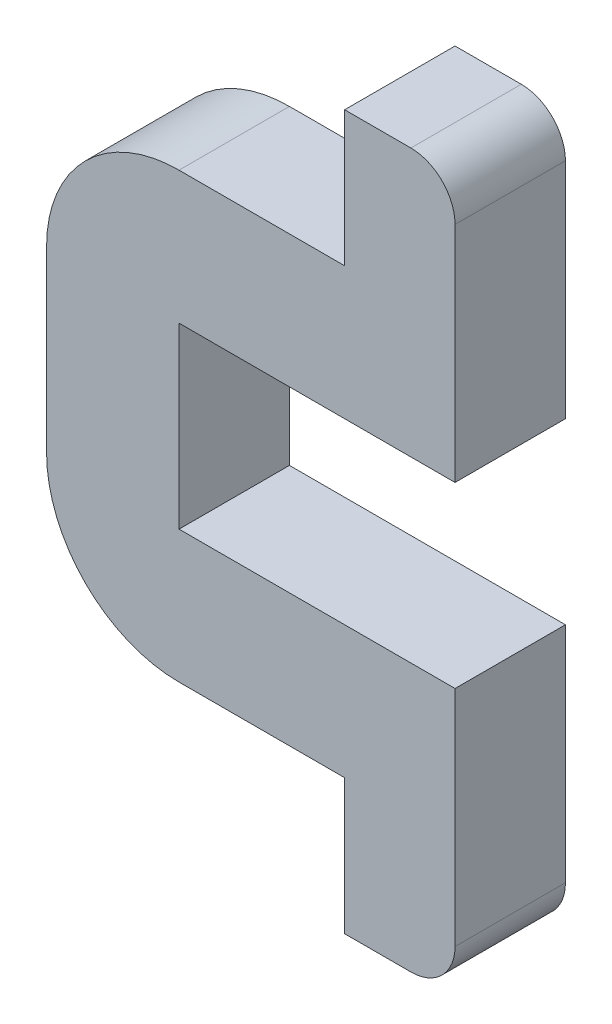
SolidWorks part; units mm, degrees
material "PBT General Purpose"
ref_plane "Front Plane" through (0, 0, 0) normal (0, 0, 1) x (1, 0, 0)
ref_plane "Top Plane" through (0, 0, 0) normal (0, 1, 0) x (1, 0, 0)
ref_plane "Right Plane" through (0, 0, 0) normal (1, 0, 0) x (0, 0, -1)
sketch "frame_outline" plane through (0, 0, 0) normal (0, 0, 1) x (1, 0, 0)
  line L0 (0, 0) -> (-0.625, 0)
  line L1 (-0.625, 0) -> (-0.625, 0.404)
  line L2 (-0.625, 0.404) -> (0, 0.404)
  line L3 (0, 0.404) -> (0, 1.01)
  line L71 (0, 1.01) -> (-0.25, 1.01)
  line L90 (-0.25, 1.01) -> (-0.25, 0.704)
  line L91 (-0.25, 0.704) -> (-0.925, 0.704)
  line L93 (-0.925, 0.704) -> (-0.925, -0.3)
  line L95 (-0.925, -0.3) -> (-0.25, -0.3)
  line L96 (-0.25, -0.3) -> (-0.25, -0.606)
  line L97 (-0.25, -0.606) -> (0, -0.606)
  line L98 (0, -0.606) -> (0, 0)
  dimension "D3" = 0.404
  dimension "D4" = 0.625
  dimension "D5" = 0.25
  dimension "D6" = 0.3
  dimension "D7" = 0.306
  dimension "D8" = 0.3
extrude "Boss-Extrude1" add sketch "frame_outline" along normal mid plane 0.25
fillet "Fillet1" radius 0.3 2 edges at (-0.925, -0.3, 0) (-0.925, 0.704, 0)
fillet "Fillet2" radius 0.1 2 edges at (0, 1.01, 0) (0, -0.606, 0)
equation "\"t\"= 0.25'thickness of the sheets"
equation "\"t_cf\" = 0.115'thickness of single carbon fiber layer"
equation "\"t_kapton\" = 0.025'thickness of single Kapton flex layer"
equation "\"t_fr4\" = 0.1'thickness of FR4 with copper layer"
equation "\"joint_flex\"= 0.1'Width of flextures gap"
equation "\"joint_flex_eff\"= 0.02'Width of flecture after castelation"
equation "\"joint_fold\"= 0.2'Width of folding joints for 90deg fold"
equation "\"gap_tolerance\"= 0.002'Width to have interfecence fit between carbon fiber inserts"
equation "\"assemble_angle\"= 90'Angle of assembly parts"
equation "\"D1@Boss-Extrude1\"=\"t\""
equation "\"D3@frame_outline\"=0.4+\"gap_tolerance\"*2"
equation "\"D4@frame_outline\"=\"t\"*2.5"
equation "\"D5@frame_outline\"=\"t\""
equation "\"D7@frame_outline\"=0.3+\"gap_tolerance\"*3"
equation "\"link_lift\"= 0.5'Actuation linkage amplification for the lift motion"
equation "\"link_swing\"= 0.45'Actuation linkage amplification for the swing motion"
